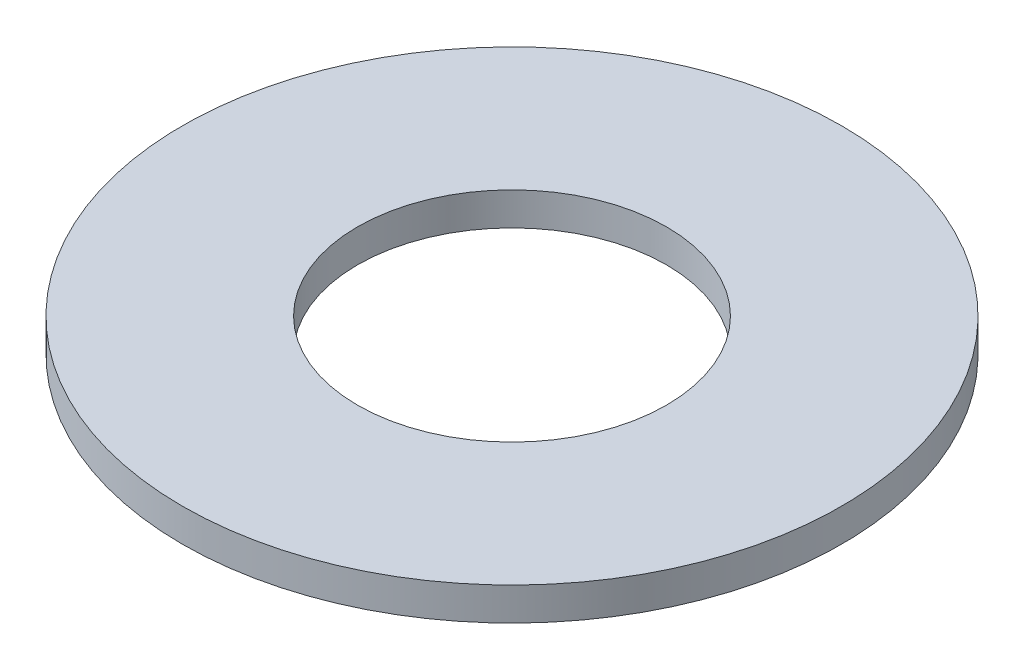
SolidWorks part; units mm, degrees
ref_plane "Front Plane" through (0, 0, 0) normal (0, 0, 1) x (1, 0, 0)
ref_plane "Top Plane" through (0, 0, 0) normal (0, 1, 0) x (1, 0, 0)
ref_plane "Right Plane" through (0, 0, 0) normal (1, 0, 0) x (0, 0, -1)
sketch "Sketch1" plane through (0, 0, 0) normal (0, 1, 0) x (1, 0, 0)
  circle A0 centre (0, 0) radius 80
  dimension "FLANGE_OD" = 160
extrude "Boss-Extrude1" add sketch "Sketch1" along normal blind 8
sketch "Sketch2" plane through (0, 0, 0) normal (0, 1, 0) x (1, 0, 0)
  circle A0 centre (0, 0) radius 37.5
  dimension "BORE_D" = 75
extrude "Cut-Extrude1" cut sketch "Sketch2" along normal through all
sketch "Sketch3" plane through (0, 8, 0) normal (0, 1, 0) x (1, 0, 0)
  circle A0 centre (0, 0) radius 27.8892 construction
  circle A1 centre (-27.8892, 0) radius 5.6479
  dimension "BOLT_D" = 11.2958
  dimension "BOLT_PCD" = 55.7783
extrude "Cut-Extrude2" cut sketch "Sketch3" against normal blind 7.6533 rebuild error yes
pattern_circular "CirPattern1" count 3 over 360 rebuild error yes
